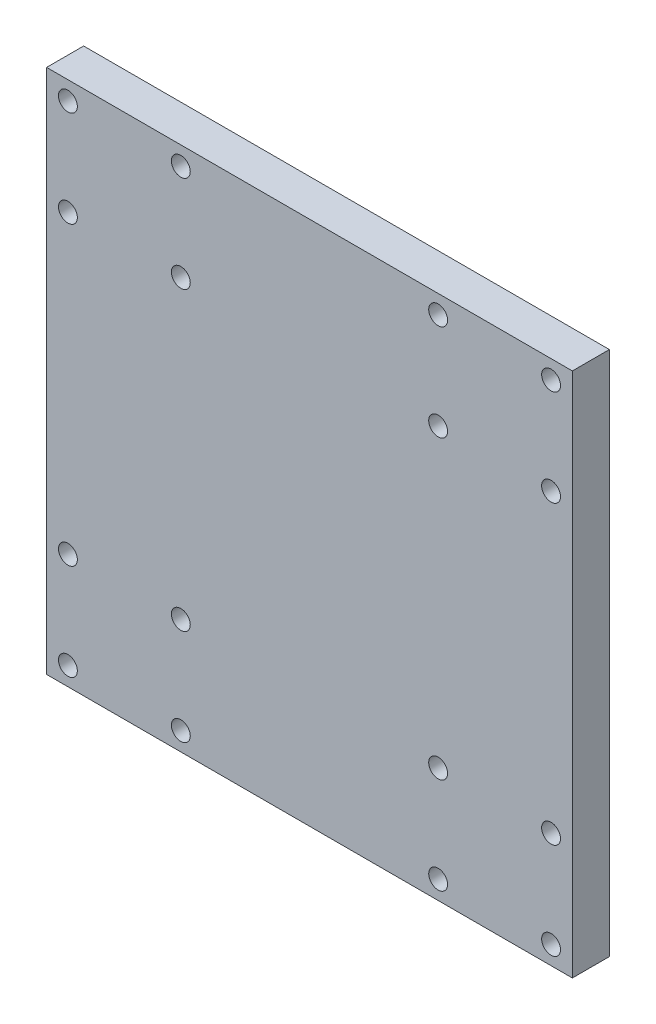
SolidWorks part; units mm, degrees
ref_plane "Front Plane" through (0, 0, 0) normal (0, 0, 1) x (1, 0, 0)
ref_plane "Top Plane" through (0, 0, 0) normal (0, 1, 0) x (1, 0, 0)
ref_plane "Right Plane" through (0, 0, 0) normal (1, 0, 0) x (0, 0, -1)
sketch "Sketch1" plane through (0, 0, 0) normal (0, 0, 1) x (1, 0, 0)
  line L1 (-71, -71) -> (71, -71)
  line L2 (-71, -71) -> (-71, 71)
  line L3 (-71, 71) -> (71, 71)
  line L4 (71, -71) -> (71, 71)
  line L5 (-71, -71) -> (71, 71) construction
  line L6 (-71, 71) -> (71, -71) construction
  point P0 (0, 0)
  dimension "D1" = 142
  dimension "D2" = 142
extrude "Boss-Extrude1" add sketch "Sketch1" along normal mid plane 10
sketch "Sketch2" plane through (0, 0, 5) normal (0, 0, 1) x (1, 0, 0)
  line L3 (-65.25, 71) -> (-65.25, -71)
  line L4 (-65.25, 71) -> (-65.25, -71) construction
  line L6 (65.25, -71) -> (65.25, 71)
  line L7 (65.25, -71) -> (65.25, 71) construction
  line L13 (-34.75, 71) -> (-34.75, -71)
  line L14 (-34.75, 71) -> (-34.75, -71) construction
  line L16 (34.75, -71) -> (34.75, 71)
  line L18 (34.75, -71) -> (34.75, 71) construction
  line L20 (71, 66) -> (-71, 66)
  line L21 (71, 66) -> (-71, 66) construction
  line L23 (-71, -66) -> (71, -66)
  line L24 (-71, -66) -> (71, -66) construction
  line L26 (71, 40) -> (-71, 40)
  line L27 (71, 40) -> (-71, 40) construction
  line L29 (-71, -40) -> (71, -40)
  line L30 (-71, -40) -> (71, -40) construction
  circle A0 centre (-65.25, 66) radius 2.55
  circle A1 centre (-34.75, 66) radius 2.55
  circle A2 centre (-34.75, 40) radius 2.55
  circle A3 centre (-65.25, 40) radius 2.55
  circle A4 centre (65.25, 66) radius 2.55
  circle A5 centre (65.25, 40) radius 2.55
  circle A6 centre (34.75, 40) radius 2.55
  circle A7 centre (34.75, 66) radius 2.55
  circle A8 centre (-65.25, -40) radius 2.55
  circle A9 centre (-34.75, -40) radius 2.55
  circle A10 centre (-34.75, -66) radius 2.55
  circle A11 centre (-65.25, -66) radius 2.55
  circle A12 centre (34.75, -40) radius 2.55
  circle A13 centre (65.25, -40) radius 2.55
  circle A14 centre (65.25, -66) radius 2.55
  circle A15 centre (34.75, -66) radius 2.55
  dimension "D9" = 5.1
  dimension "D10" = 5.1
  dimension "D11" = 5.1
  dimension "D12" = 5.1
  dimension "D13" = 5.1
  dimension "D14" = 5.1
  dimension "D15" = 5.1
  dimension "D16" = 5.1
  dimension "D17" = 5.1
  dimension "D18" = 5.1
  dimension "D19" = 5.1
  dimension "D20" = 5.1
  dimension "D21" = 5.1
  dimension "D22" = 5.1
  dimension "D23" = 5.1
  dimension "D24" = 5.1
  dimension "D1" = 5.75
  dimension "D2" = 5.75
  dimension "D3" = 36.25
  dimension "D4" = 36.25
  dimension "D5" = 5
  dimension "D6" = 5
  dimension "D7" = 31
  dimension "D8" = 31
extrude "Cut-Extrude1" cut sketch "Sketch2" against normal through all
